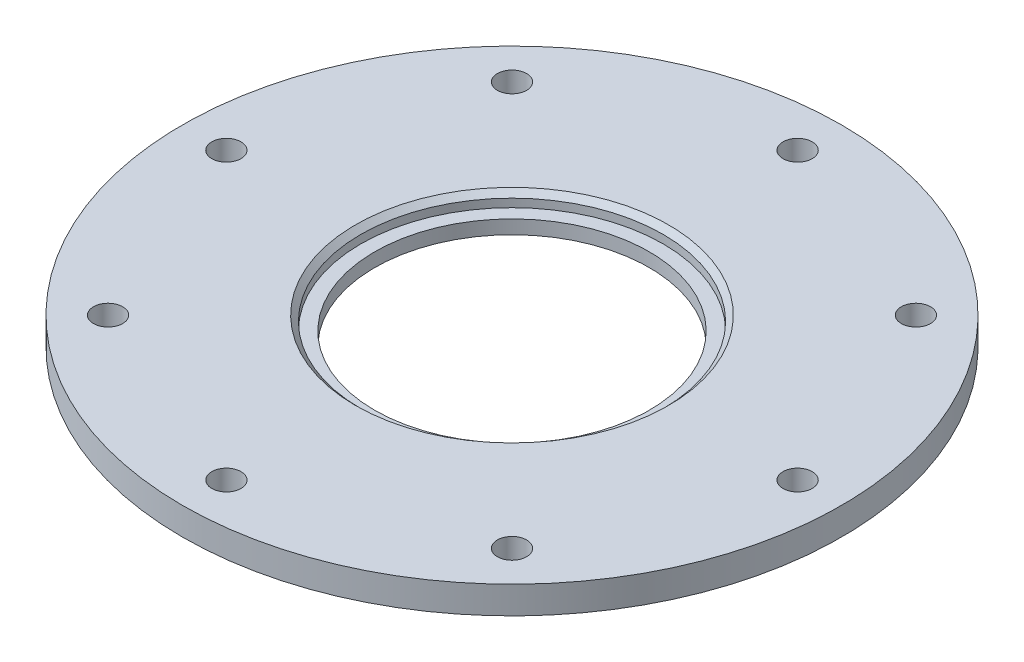
SolidWorks part; units mm, degrees
material "AISI 304"
ref_plane "Front Plane" through (0, 0, 0) normal (0, 0, 1) x (1, 0, 0)
ref_plane "Top Plane" through (0, 0, 0) normal (0, 1, 0) x (1, 0, 0)
ref_plane "Right Plane" through (0, 0, 0) normal (1, 0, 0) x (0, 0, -1)
sketch "Sketch1" plane through (0, 0, 0) normal (0, 1, 0) x (1, 0, 0)
  circle A0 centre (0, 0) radius 34.925
  circle A1 centre (0, 0) radius 76.2
  dimension "D1" = 69.85
  dimension "D2" = 152.4
extrude "Boss-Extrude1" add sketch "Sketch1" along normal blind 6.35
hole_wizard "1/4 Clearance Hole1" positions "Sketch5" profile "Sketch4" hole size "1/4" standard "ANSI Inch"
sketch "Sketch5" plane through (0, 6.35, 0) normal (0, 1, 0) x (1, 0, 0)
  line L0 (0, 0) -> (0, -50000) construction
  point P0 (0, -66.04)
  dimension "D1" = 66.04
sketch "Sketch4" plane through (0, 6.35, 66.04) normal (1, 0, 0) x (0, 0, 1)
  line L0 (0, 0) -> (0, 27.4298)
  line L1 (0, 27.4298) -> (3.3782, 25.4)
  line L2 (3.3782, 25.4) -> (3.3782, 0)
  line L5 (3.3782, 0) -> (0, 0)
  line L10 (0, 27.4298) -> (-3.3782, 25.4) construction
  line L11 (0, -6.35) -> (0, 107.95) construction
  dimension "Hole Dia." = 6.7564
  dimension "Hole Depth" = 25.4
  dimension "Drill Angle" = 118
ref_axis "Axis1" through (0, 6.6675, 0) along (0, -1, 0)
pattern_circular "CirPattern1" count 8 over 360 about axis through (0, 6.6675, 0) along (0, -1, 0) of "1/4 Clearance Hole1"
chamfer "Chamfer1" distance 1.27 angle 45 1 edges at (0, 6.35, 34.925)
sketch "Sketch6" plane through (0, 0, 0) normal (0, 1, 0) x (1, 0, 0)
  circle A0 centre (0, 0) radius 31.75
  circle A1 centre (0, 0) radius 34.925
  circle A2 centre (0, 0) radius 34.925 construction
  dimension "D1" = 63.5
extrude "Boss-Extrude2" add sketch "Sketch6" along normal blind 3.175
